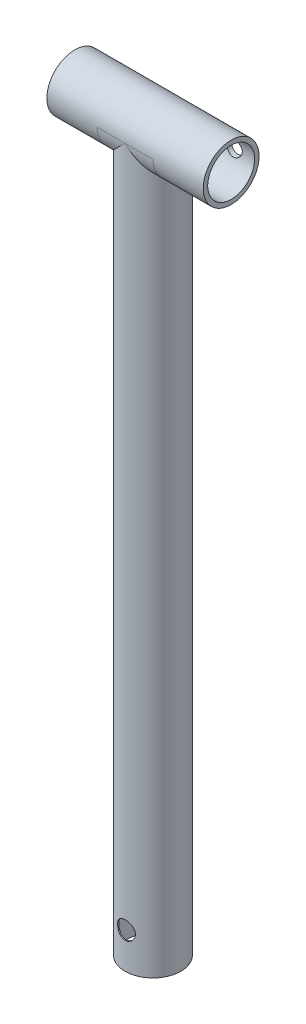
SolidWorks part; units mm, degrees
material "Aleación 1060"
ref_plane "Alzado" through (0, 0, 0) normal (0, 0, 1) x (1, 0, 0)
ref_plane "Planta" through (0, 0, 0) normal (0, 1, 0) x (1, 0, 0)
ref_plane "Vista lateral" through (0, 0, 0) normal (1, 0, 0) x (0, 0, -1)
sketch "Croquis1" plane through (0, 0, 0) normal (0, 1, 0) x (1, 0, 0)
  circle A0 centre (0, 0) radius 12.5
  dimension "D1" = 25
extrude "Saliente-Extruir1" add sketch "Croquis1" along normal blind 320
sketch "Croquis2" plane through (0, 320, 0) normal (0, 1, 0) x (1, 0, 0)
  circle A0 centre (0, 0) radius 12
  circle A1 centre (0, 12.5) radius 1.5
  circle A2 centre (0, 0) radius 12.5 construction
  dimension "D1" = 24
  dimension "D2" = 3
extrude "Cortar-Extruir8" cut sketch "Croquis2" against normal through all contours A1 A0 region at (0, 320, 0.051)
sketch "Croquis5" plane through (0, 320, 0) normal (0, 1, 0) x (1, 0, 0)
  circle A0 centre (0, 12.5) radius 1
  circle A1 centre (0, 0) radius 12.5 construction
  dimension "D1" = 2
extrude "Cortar-Extruir9" cut sketch "Croquis5" against normal through all
sketch "Croquis6" plane through (0, 320, 0) normal (0, 1, 0) x (1, 0, 0)
  circle A0 centre (0, 0) radius 12.5
extrude "Saliente-Extruir2" add sketch "Croquis6" along normal blind 1
sketch "Croquis7" plane through (0, 321, 0) normal (0, 1, 0) x (1, 0, 0)
  line L1 (-35, -12.5) -> (35, -12.5)
  line L2 (-35, -12.5) -> (-35, 12.5)
  line L3 (-35, 12.5) -> (35, 12.5)
  line L4 (35, -12.5) -> (35, 12.5)
  line L5 (-35, -12.5) -> (35, 12.5) construction
  line L6 (-35, 12.5) -> (35, -12.5) construction
  point P0 (0, 0)
  dimension "D1" = 70
  dimension "D2" = 25
extrude "Saliente-Extruir4" add sketch "Croquis7" along normal mid plane 25
sketch "Croquis10" plane through (35, 0, 0) normal (1, 0, 0) x (0, 0, -1)
  line L0 (0, 333.5) -> (0, 308.5) construction
  line L1 (-12.5, 333.5) -> (12.5, 333.5) construction
  line L2 (-12.5, 308.5) -> (12.5, 308.5) construction
  line L3 (-12.5, 333.5) -> (12.5, 333.5)
  line L4 (12.5, 333.5) -> (12.5, 308.5)
  line L5 (12.5, 308.5) -> (-12.5, 308.5)
  line L6 (-12.5, 308.5) -> (-12.5, 333.5)
  circle A0 centre (0, 321) radius 12.5
  line M4 (12.5, 333.5) -> (-12.5, 333.5)
  line M5 (-12.5, 333.5) -> (-12.5, 308.5)
extrude "Cortar-Extruir12" cut sketch "Croquis10" against normal through all contours A0 L3 M5 | A0 L4 M4 region at (35, 330.7079, 9.7079) region at (35, 330.7079, -9.7079)
sketch "Croquis11" plane through (35, 0, 0) normal (1, 0, 0) x (0, 0, -1)
  line L0 (0, 333.5) -> (0, 308.5) construction
  line L1 (-12.5, 308.5) -> (12.5, 308.5) construction
  line L2 (12.5, 321) -> (12.5, 308.5)
  line L3 (12.5, 308.5) -> (-12.5, 308.5)
  line L4 (-12.5, 321) -> (-12.5, 308.5)
  arc A0 (12.5, 321) -> (-12.5, 321) centre (0, 321) ccw construction
  circle A1 centre (0, 321) radius 12.5
  line M2 (12.5, 308.5) -> (12.5, 321)
  line M4 (-12.5, 321) -> (-12.5, 308.5)
  line M5 (-12.5, 308.5) -> (12.5, 308.5)
extrude "Cortar-Extruir13" cut sketch "Croquis11" against normal blind 22.5 contours A1 L3 M2 | A1 M4 M5 region at (35, 311.2921, -9.7079) region at (35, 311.2921, 9.7079)
sketch "Croquis12" plane through (-35, 0, 0) normal (-1, 0, 0) x (0, 0, 1)
  line L0 (0, 333.5) -> (0, 308.5) construction
  line L1 (-12.5, 308.5) -> (12.5, 308.5) construction
  line L2 (-12.5, 321) -> (-12.5, 308.5)
  line L3 (-12.5, 308.5) -> (12.5, 308.5)
  line L4 (12.5, 308.5) -> (12.5, 321)
  arc A0 (12.5, 321) -> (-12.5, 321) centre (0, 321) ccw construction
  circle A1 centre (0, 321) radius 12.5
  line M2 (-12.5, 321) -> (-12.5, 308.5)
  line M3 (-12.5, 308.5) -> (12.5, 308.5)
  line M4 (12.5, 308.5) -> (12.5, 321)
extrude "Cortar-Extruir14" cut sketch "Croquis12" against normal blind 22.5 contours A1 M2 M3 | A1 L3 M4 region at (-35, 311.2921, -9.7079) region at (-35, 311.2921, 9.7079)
fillet "Redondeo3" radius 12.5 2 edges at (6.25, 308.5, 12.5) (-6.25, 308.5, 12.5)
fillet "Redondeo6" radius 12.5 1 edges at (0, 308.5, -12.5)
sketch "Croquis13" plane through (35, 0, 0) normal (1, 0, 0) x (0, 0, -1)
  line L0 (0, 333.5) -> (0, 308.5) construction
  circle A0 centre (0, 321) radius 12.5 construction
  circle A1 centre (0, 321) radius 10.5
  dimension "D1" = 21
ref_plane "Plano1" through (0, 0, -12.5) normal (0, 0, -1) x (-1, 0, 0)
sketch "Croquis14" plane through (0, 0, -12.5) normal (0, 0, -1) x (-1, 0, 0)
  line L0 (0, 321) -> (-26, 321) construction
  line L1 (12.5, 321) -> (-12.5, 321) construction
  line L2 (-35, 333.5) -> (-35, 308.5) construction
  line L3 (0, 321) -> (0, 323.6076) construction
  circle A0 centre (-26, 321) radius 3.5
  circle A1 centre (26, 321) radius 3.5
  dimension "D2" = 7
  dimension "D1" = 9
extrude "Cortar-Extruir16" cut sketch "Croquis13" against normal through all
extrude "Cortar-Extruir17" cut sketch "Croquis14" against normal mid plane 12.5
sketch3d "Croquis3D1"
  point P0 (0.1476, 15.6083, 12.4991)
ref_plane "Plano2" through (0, 0, 12.4991) normal (0, 0, 1) x (1, 0, 0)
sketch "Croquis15" plane through (0, 0, 12.4991) normal (0, 0, 1) x (1, 0, 0)
  circle A0 centre (0, 16) radius 4
  dimension "D1" = 8
  dimension "D2" = 16
extrude "Cortar-Extruir19" cut sketch "Croquis15" against normal mid plane 10
